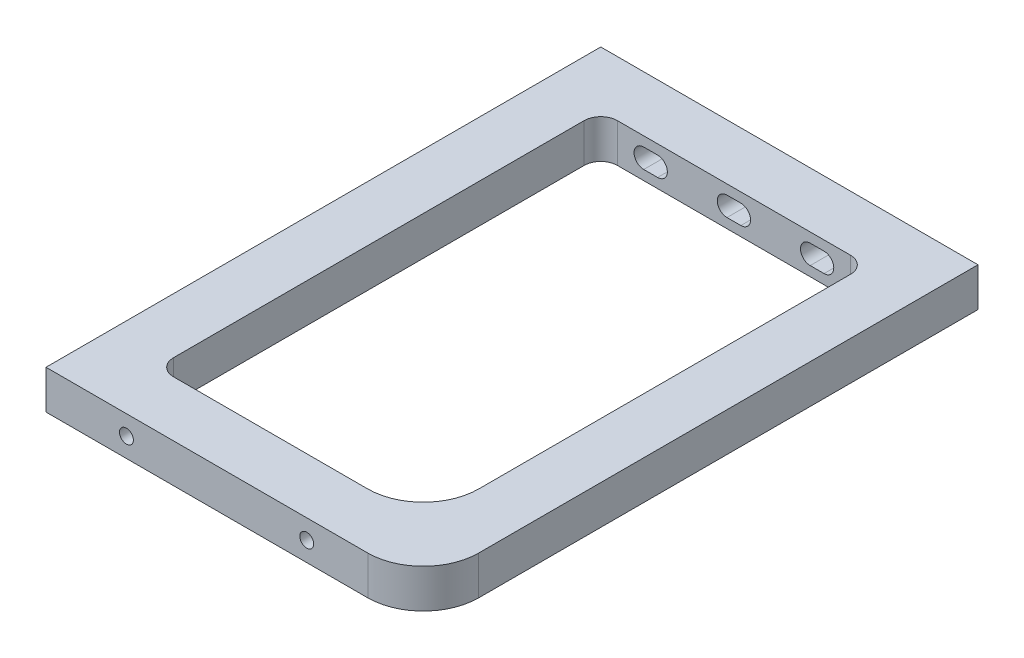
SolidWorks part; units mm, degrees
other "Markup1"
sketch "Sketch11" plane through (-148, 207, 138) normal (-0.4174, 0.5856, 0.6948) x (0.7295, -0.24, 0.6405)
ref_plane "Front Plane" through (0, 0, 0) normal (0, 0, 1) x (1, 0, 0)
ref_plane "Top Plane" through (0, 0, 0) normal (0, 1, 0) x (1, 0, 0)
ref_plane "Right Plane" through (0, 0, 0) normal (1, 0, 0) x (0, 0, -1)
sketch "Sketch1" plane through (0, 0, 0) normal (0, 0, 1) x (1, 0, 0)
  line L1 (-148, 230) -> (-148, 165) construction
  line L4 (-148, 207) -> (-21, 207)
  line L7 (-148, 197.5) -> (-148, 192.5) construction
  line L8 (-148, 197.5) -> (-148, 192.5)
  line L9 (-148, 192.5) -> (-148, 193)
  line L10 (-148, 197.5) -> (-148, 207)
  line L11 (-148, 193) -> (-24, 193)
  line L13 (-148, 207) -> (-21, 207)
  line L16 (-21, 207) -> (-12, 207)
  line L17 (-12, 207) -> (-12, 193)
  line L18 (-12, 193) -> (-24, 193)
extrude "Boss-Extrude1" add sketch "Sketch1" along normal up to surface (200 mm away) contours L4 L10 L8 L9 L11 region at (-80, 200, 0)
sketch "Sketch3" plane through (0, 207, 0) normal (0, 1, 0) x (1, 0, 0)
  line L0 (-128, -30) -> (-128, -20)
  line L1 (-128, -108) -> (-128, -180)
  line L2 (-128, -180) -> (-118, -180)
  line L3 (-54, -180) -> (-32, -180)
  line L4 (-32, -180) -> (-32, -20)
  line L5 (-32, -180) -> (-32, -20)
  line L6 (-32, -20) -> (-128, -20)
  line L7 (-32, -20) -> (-128, -20)
  line L12 (-128, -20) -> (-128, -180)
  line L13 (-128, -20) -> (-128, -180)
  line L23 (-128, -180) -> (-32, -180)
  line L27 (-118, -180) -> (-54, -180)
  dimension "D1" = 20
extrude "Cut-Extrude1" cut sketch "Sketch3" against normal through all contours L7 L13 L27 region at (-80, 207, 100)
sketch "Sketch5" plane through (0, 0, 20) normal (0, 0, 1) x (1, 0, 0)
  circle A3 centre (-110, 200) radius 3
  circle A4 centre (-80, 200) radius 3
  circle A5 centre (-50, 200) radius 3
hole_wizard "Ø6.0mm Dowel Slot1" positions "Sketch6" profile "Sketch7" size "Ø6.0" standard "ANSI Metric" slot yes end condition through all
sketch "Sketch6" plane through (0, 0, 20) normal (0, 0, 1) x (1, 0, 0)
  line L0 (-116, 200) -> (-104, 200) construction
  point P12 (-110, 200)
  point P15 (-80, 200)
  point P18 (-50, 200)
  dimension "D1" = 12
sketch "Sketch7" plane through (-110, 200, 20) normal (1, 0, 0) x (0, -1, 0)
  line L0 (0, 0) -> (0, 20)
  line L1 (0, 20) -> (3.5, 20)
  line L2 (3.5, 20) -> (3.5, 0)
  line L5 (3.5, 0) -> (0, 0)
  line L11 (0, -6.35) -> (0, 107.95) construction
  dimension "Thru Hole Dia." = 7
  dimension "Thru Hole Depth" = 20
sketch "Sketch8" plane through (0, 0, 200) normal (0, 0, 1) x (1, 0, 0)
  line L0 (-48, 200) -> (-54, 200)
  line L2 (-148, 200) -> (-119, 200)
hole_wizard "M6x1.0 Tapped Hole1" positions "Sketch9" profile "Sketch10" tap size "M6x1.0" standard "ANSI Metric"
sketch "Sketch9" plane through (0, 0, 200) normal (0, 0, 1) x (1, 0, 0)
  point P0 (-119, 200)
  point P3 (-54, 200)
sketch "Sketch10" plane through (-119, 200, 200) normal (1, 0, 0) x (0, -1, 0)
  line L0 (0, 0) -> (0, 23)
  line L1 (0, 23) -> (2.5, 21.4978)
  line L2 (2.5, 21.4978) -> (2.5, 0)
  line L5 (2.5, 0) -> (0, 0)
  line L10 (0, 23) -> (-2.5, 21.4978) construction
  line L11 (0, -6.35) -> (0, 107.95) construction
  dimension "Tap Drill Dia." = 5
  dimension "Tap Drill Depth" = 23
  dimension "Drill Angle" = 118
cosmetic thread "Hole Thread1" parameters "D1"=20, "D2"=6
cosmetic thread "Hole Thread2" parameters "D1"=20, "D2"=6
fillet "Fillet1" radius 6 3 edges at (-128, 200, 180) (-128, 200, 20) (-32, 200, 20)
fillet "Fillet2" radius 20 2 edges at (-12, 200, 200) (-32, 200, 180)
